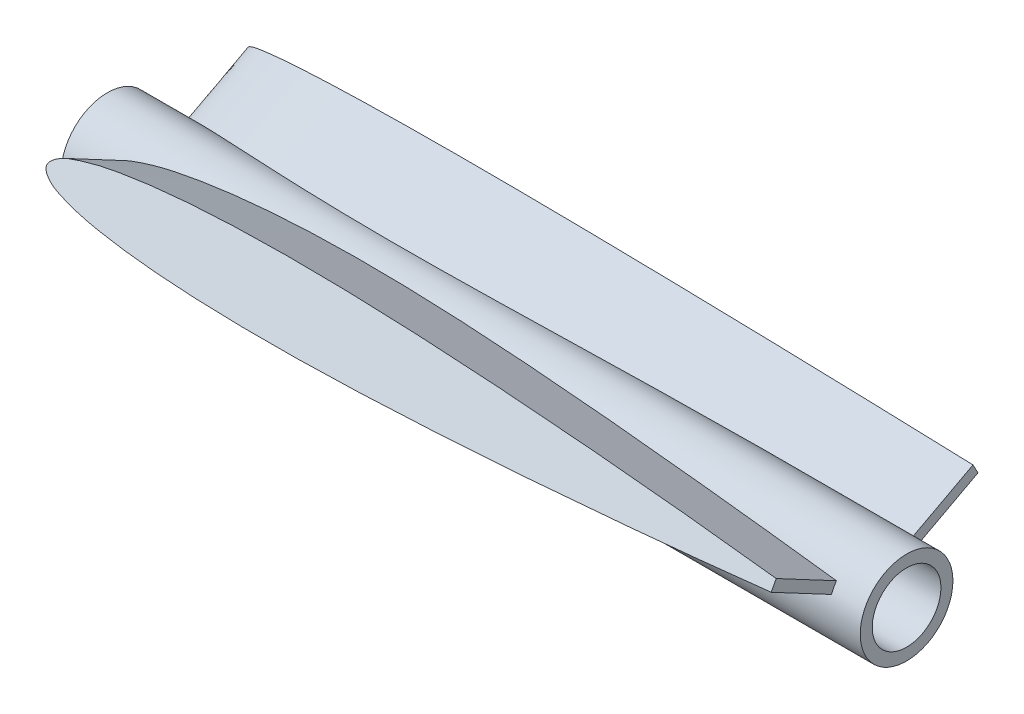
SolidWorks part; units mm, degrees
ref_plane "Front Plane" through (0, 0, 0) normal (0, 0, 1) x (1, 0, 0)
ref_plane "Top Plane" through (0, 0, 0) normal (0, 1, 0) x (1, 0, 0)
ref_plane "Right Plane" through (0, 0, 0) normal (1, 0, 0) x (0, 0, -1)
sketch "Эскиз4" plane through (0, 0, 0) normal (0, 0, 1) x (1, 0, 0)
  line L0 (0, 0) -> (-190.9268, 0) construction
ref_plane "Плоскость2" through (0, 0, 0) normal (0, -0.4695, 0.8829) x (-1, 0, 0)
curve "Кривая2"
  spline degree 3 poles (195, 0.1446, 0.0769) (191.7503, 0.4076, 0.2167) (185.2523, 0.9335, 0.4963) (172.2543, 1.9127, 1.0169) (156.0064, 3.0366, 1.6144) (136.5058, 4.2319, 2.2499) (117.0061, 5.2717, 2.8027) (97.5059, 6.116, 3.2517) (78.0051, 6.72, 3.5728) (61.7506, 6.9306, 3.6848) (48.7484, 6.8474, 3.6405) (38.9957, 6.6202, 3.5197) (29.2371, 6.1855, 3.2886) (21.113, 5.5745, 2.9638) (14.6037, 4.8451, 2.576) (9.7375, 4.1386, 2.2003) (5.5568, 3.2162, 1.7099) (2.2726, 2.2745, 1.2092) (-1.296, 0, 0) (2.2726, -2.2745, -1.2092) (5.5568, -3.2162, -1.7099) (9.7375, -4.1386, -2.2003) (14.6037, -4.8451, -2.576) (21.113, -5.5745, -2.9638) (29.2371, -6.1855, -3.2886) (38.9957, -6.6202, -3.5197) (48.7484, -6.8474, -3.6405) (61.7506, -6.9306, -3.6848) (78.0051, -6.72, -3.5728) (97.5059, -6.116, -3.2517) (117.0061, -5.2717, -2.8027) (136.5058, -4.2319, -2.2499) (156.0064, -3.0366, -1.6144) (172.2543, -1.9127, -1.0169) (185.2523, -0.9335, -0.4963) (191.7503, -0.4076, -0.2167) (195, -0.1446, -0.0769) knots 0 0 0 0 0.024876 0.049742 0.099443 0.149112 0.198751 0.248359 0.297937 0.347491 0.372267 0.397051 0.421859 0.446731 0.45922 0.471791 0.48456 0.491195 0.5 0.508805 0.51544 0.528209 0.54078 0.553269 0.578141 0.602949 0.627733 0.652509 0.702063 0.751641 0.801249 0.850888 0.900557 0.950258 0.975124 1 1 1 1
sketch "Эскиз5" plane through (0, 0, 0) normal (0, -0.4695, 0.8829) x (-1, 0, 0)
  line L0 (-182, -1.3314) -> (-182, 1.3314)
  line L1 (0, 0) -> (0, -20.2138) construction
  spline S0 degree 3 poles (-1090.5141, -2820.9233) (-613.9595, 82.5122) (-398.4311, 17.1316) (-172.2543, -2.1663) (-156.0064, -3.439) (-136.5058, -4.7928) (-117.0061, -5.9704) (-97.5059, -6.9267) (-78.0051, -7.6107) (-61.7506, -7.8493) (-48.7484, -7.755) (-38.9957, -7.4977) (-29.2371, -7.0053) (-21.113, -6.3134) (-14.6037, -5.4873) (-9.7375, -4.6872) (-5.5568, -3.6425) (-2.2726, -2.5759) (1.296, 0) (-2.2726, 2.5759) (-5.5568, 3.6425) (-9.7375, 4.6872) (-14.6037, 5.4873) (-21.113, 6.3134) (-29.2371, 7.0053) (-38.9957, 7.4977) (-48.7484, 7.755) (-61.7506, 7.8493) (-78.0051, 7.6107) (-97.5059, 6.9267) (-117.0061, 5.9704) (-136.5058, 4.7928) (-156.0064, 3.439) (-172.2543, 2.1663) (-398.4306, -17.1316) (-613.9586, -82.5119) (-1090.511, 2820.9046) knots -1.630961 -1.630961 -1.630961 -1.630961 0.024876 0.049742 0.099443 0.149112 0.198751 0.248359 0.297937 0.347491 0.372267 0.397051 0.421859 0.446731 0.45922 0.471791 0.48456 0.491195 0.5 0.508805 0.51544 0.528209 0.54078 0.553269 0.578141 0.602949 0.627733 0.652509 0.702063 0.751641 0.801249 0.850888 0.900557 0.950258 0.975124 2.630958 2.630958 2.630958 2.630958 only from (-195, -0.1638) to (-195, 0.1638) construction
  spline S1 degree 3 poles (-182, -1.3314) (-179.8337, -1.5187) (-171.1702, -2.2512) (-156.0064, -3.439) (-136.5058, -4.7928) (-117.0061, -5.9704) (-97.5059, -6.9267) (-78.0051, -7.6107) (-61.7506, -7.8493) (-48.7484, -7.755) (-38.9957, -7.4977) (-29.2371, -7.0053) (-21.113, -6.3134) (-14.6037, -5.4873) (-9.7375, -4.6872) (-5.5568, -3.6425) (-2.2726, -2.5759) (0, -0.9355) (0, 0) knots 0.033166 0.033166 0.033166 0.033166 0.049742 0.099443 0.149112 0.198751 0.248359 0.297937 0.347491 0.372267 0.397051 0.421859 0.446731 0.45922 0.471791 0.48456 0.491195 0.5 0.5 0.5 0.5
  spline S2 degree 3 poles (0, 0) (0, 0.9355) (-2.2726, 2.5759) (-5.5568, 3.6425) (-9.7375, 4.6872) (-14.6037, 5.4873) (-21.113, 6.3134) (-29.2371, 7.0053) (-38.9957, 7.4977) (-48.7484, 7.755) (-61.7506, 7.8493) (-78.0051, 7.6107) (-97.5059, 6.9267) (-117.0061, 5.9704) (-136.5058, 4.7928) (-156.0064, 3.439) (-171.1702, 2.2512) (-179.8337, 1.5187) (-182, 1.3314) knots 0.5 0.5 0.5 0.5 0.508805 0.51544 0.528209 0.54078 0.553269 0.578141 0.602949 0.627733 0.652509 0.702063 0.751641 0.801249 0.850888 0.900557 0.950258 0.966834 0.966834 0.966834 0.966834
  dimension "D1" = 182
sketch "Эскиз6" plane through (0, 0, 0) normal (1, 0, 0) x (0, 0, -1)
  line L0 (0, 0) -> (17.6146, 0) construction
  line L1 (0, 0) -> (-25.2523, -13.4269) construction
  line L2 (-25.2523, -4.8269) -> (-25.2523, -22.0269) construction
  circle A0 centre (-25.2523, -13.4269) radius 8.6
  circle A1 centre (-25.2523, -13.4269) radius 11.6
  dimension "D2" = 17.2
  dimension "D3" = 20
  dimension "D1" = 28
  dimension "D4" = 3
extrude "Бобышка-Вытянуть1" add sketch "Эскиз6" along normal blind 190 and the other way blind 10
extrude "Бобышка-Вытянуть2" add sketch "Эскиз5" along normal up to body separate body
ref_plane "Плоскость3" through (0, 0, 25.2523) normal (0, 0, 1) x (1, 0, 0)
mirror "Зеркальное отражение1" about plane through (0, 0, 25.2523) normal (0, 0, 1) of "Бобышка-Вытянуть2"
equation "\"D6@Fus\"=\"DMotor\"+1.2"
equation "\"D1@Fus\"=\"FusLenght\""
equation "\"D2@Fus\"=\"MotorArm\""
equation "\"D4@Fus\"=\"DFus\""
equation "\"D5@Fus\" = \"FusCentralPartLenght\""
equation "\"D8@Fus\"=\"FusTubeHeight\""
equation "\"D9@Fus\"=\"DTailTube\"+1.2"
equation "\"D11@Fus\"=\"FusNoseLenght\""
equation "\"D3@Fus\"=\"WingOffset\""
equation "\"D19@Бобышка-Вытянуть1\" = \"CenterSectionLenght\" / 2"
equation "\"D4@FusCopy\" = \"FusTubeHeight\""
equation "\"D1@CentralPartCrossSection1\"=\"DFus\"*\"EllipseRatio\""
equation "\"D1@CentralPartCrossSection2\"=\"DFus\"*\"EllipseRatio\""
equation "\"D2@Frame\" = \"DFusTube\" + 1.2"
equation "\"DTailTube\"= 16mm'Диаметр трубки хвостового оперения"
equation "\"FusLenght\"= 700mm"
equation "\"DMotor\"= 35.2mm"
equation "\"MotorArm\"= 225mm"
equation "\"DFus\"= 140mm"
equation "\"DFusTube\"= 30mm'Диаметр трубки внутри фюзеляжа"
equation "\"FusTubeHeight\"= 40mm"
equation "\"FusCentralPartLenght\"= 350mm"
equation "\"FusNoseLenght\"= 170mm"
equation "\"WingOffset\"= 1mm'Расстояние от внутренней поверхности фюзеляжа до профиля крыла по вертикали"
equation "\"EllipseRatio\"= 0.95'Центральная часть фюзеляжа - эллипс. Этот параметр - отношение длин осей эллипса"
equation "\"FrameOffset\"= 0.6mm"
equation "\"DThreadedInsert\"= 3.6mm'Внешний диамер резьбовых втулок"
equation "\"CenterSectionLenght\"= 140mm'Длина центроплана"
equation "\"b\"= 1700mm'Размах"
equation "\"cwr\"= 236mm'Корневая хорда крыла"
equation "\"TR\"= 0.75'Сужение крыла"
equation "\"cwt\"= \"TR\" * \"cwr\"'Концевая хорда крыла"
equation "\"D3@Airfoil\"=\"cwr\""
equation "\"DWingMainSpar\"= 16mm'Диаметр главного лонжерона крыла"
equation "\"DWingSecondSpar\"= 8mm'Диаметр второго лонжерона крыла"
equation "\"WingSparsDistance\"= 80mm'Расстояния между отверстиями по лонжерон крыла"
equation "\"D7@Airfoil\"=\"DWingMainSpar\""
equation "\"D9@Airfoil\"=\"DWingSecondSpar\""
equation "\"D8@Airfoil\"=\"WingSparsDistance\"*2"
equation "\"c\"= 210mm'САХ крыла"
equation "\"D2@Эскиз6\"=\"DTailTube\"+1.2"
equation "\"D19@Вырез-Вытянуть2\"=\"DFus\"/2+10"
equation "\"FusTubeLenght\"= \"FusCentralPartLenght\" + \"FusNoseLenght\" + 10mm'Длина трубки фюзеляжа"
equation "\"bt\"=291mm'Высота лопатки хвоста"
equation "\"TailTubeLenght\"=700mm'Длина хвостовой балки"
equation "\"DStringer\"=6mm'Диаметр стрингеров"
equation "\"TailConnectorBaseLenght\"=20mm'Высота основания конектора хвоста"
equation "\"D3@Эскиз6\"=\"TailConnectorBaseLenght\""
